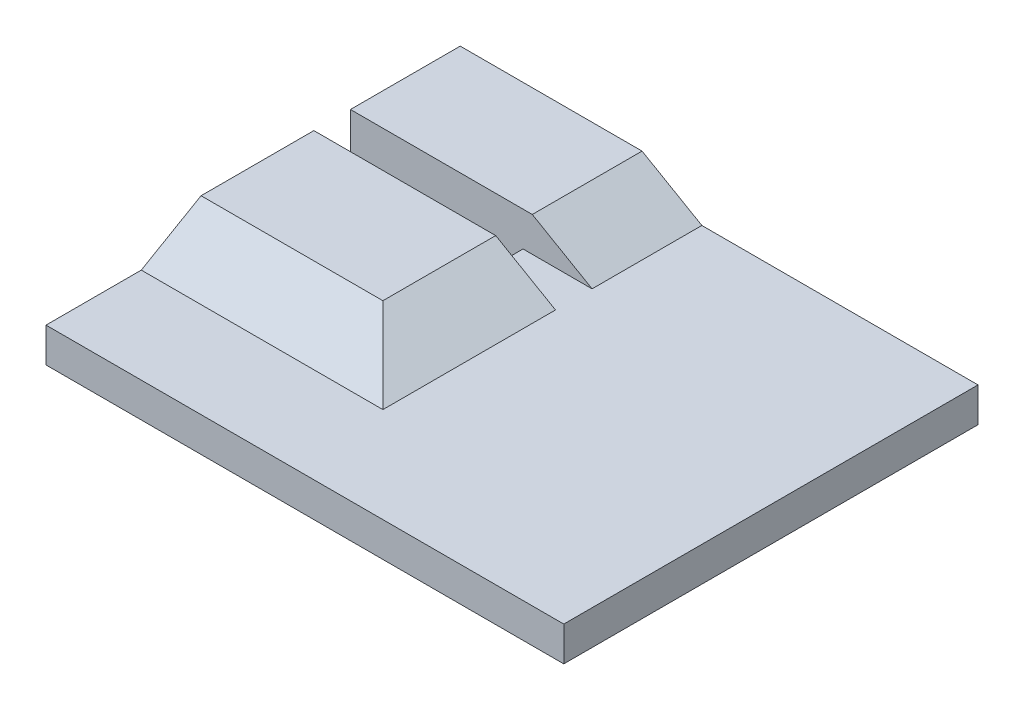
SolidWorks part; units mm, degrees
ref_plane "Front Plane" through (0, 0, 0) normal (0, 0, 1) x (1, 0, 0)
ref_plane "Top Plane" through (0, 0, 0) normal (0, 1, 0) x (1, 0, 0)
ref_plane "Right Plane" through (0, 0, 0) normal (1, 0, 0) x (0, 0, -1)
sketch "Sketch1" plane through (0, 0, 0) normal (0, 1, 0) x (1, 0, 0)
  line L1 (-18.75, -20) -> (18.75, -20)
  line L2 (-18.75, -20) -> (-18.75, 20)
  line L3 (-18.75, 20) -> (18.75, 20)
  line L4 (18.75, -20) -> (18.75, 20)
  line L5 (-18.75, -20) -> (18.75, 20) construction
  line L6 (-18.75, 20) -> (18.75, -20) construction
  point P0 (0, 0)
  dimension "D1" = 40
  dimension "D2" = 37.5
extrude "Boss-Extrude1" add sketch "Sketch1" along normal blind 2.5
sketch "Sketch2" plane through (0, 0, 0) normal (0, -1, 0) x (1, 0, 0)
  line L0 (-18.75, -20) -> (-18.75, 20) construction
  line L1 (-18.75, 0.6) -> (-6.25, 0.6)
  line L2 (-18.75, 0.6) -> (-18.75, -2.05)
  line L3 (-18.75, -2.05) -> (-6.25, -2.05)
  line L4 (-6.25, 0.6) -> (-6.25, -2.05)
  dimension "D1" = 2.65
  dimension "D2" = 12.5
  dimension "D3" = 0.6
extrude "Cut-Extrude1" cut sketch "Sketch2" against normal through all
sketch "Sketch3" plane through (0, 2.5, 0) normal (0, 1, 0) x (1, 0, 0)
  line L0 (18.75, 20) -> (-18.75, 20) construction
  line L1 (-18.75, 2.05) -> (-6.25, 2.05)
  line L2 (-18.75, 2.05) -> (-18.75, 20)
  line L3 (-18.75, 20) -> (-6.25, 20)
  line L4 (-6.25, 2.05) -> (-6.25, 20)
  line L5 (-6.25, 2.05) -> (-6.25, -0.6) construction
  line L7 (-18.75, -0.6) -> (-6.25, -0.6)
  line L8 (-18.75, -0.6) -> (-18.75, -8.1)
  line L9 (-18.75, -8.1) -> (-6.25, -8.1)
  line L10 (-6.25, -0.6) -> (-6.25, -8.1)
  dimension "D1" = 7.5
extrude "Boss-Extrude2" add sketch "Sketch3" along normal blind 2.5
sketch "Sketch4" plane through (0, 5, 0) normal (0, 1, 0) x (1, 0, 0)
  line L1 (-18.75, 20) -> (18.75, 20)
  line L2 (-18.75, 20) -> (-18.75, 10)
  line L3 (-18.75, 10) -> (18.75, 10)
  line L4 (18.75, 20) -> (18.75, 10)
  line L5 (18.75, -20) -> (18.75, 20) construction
  dimension "D1" = 10
extrude "Cut-Extrude2" cut sketch "Sketch4" against normal through all
chamfer "Chamfer1" distance 5 angle 30 3 edges at (-6.25, 2.5, -6.025) (-12.5, 2.5, 8.1) (-6.25, 2.5, 4.35) first distance on face at (-3.125, 2.5, 4.3437)
